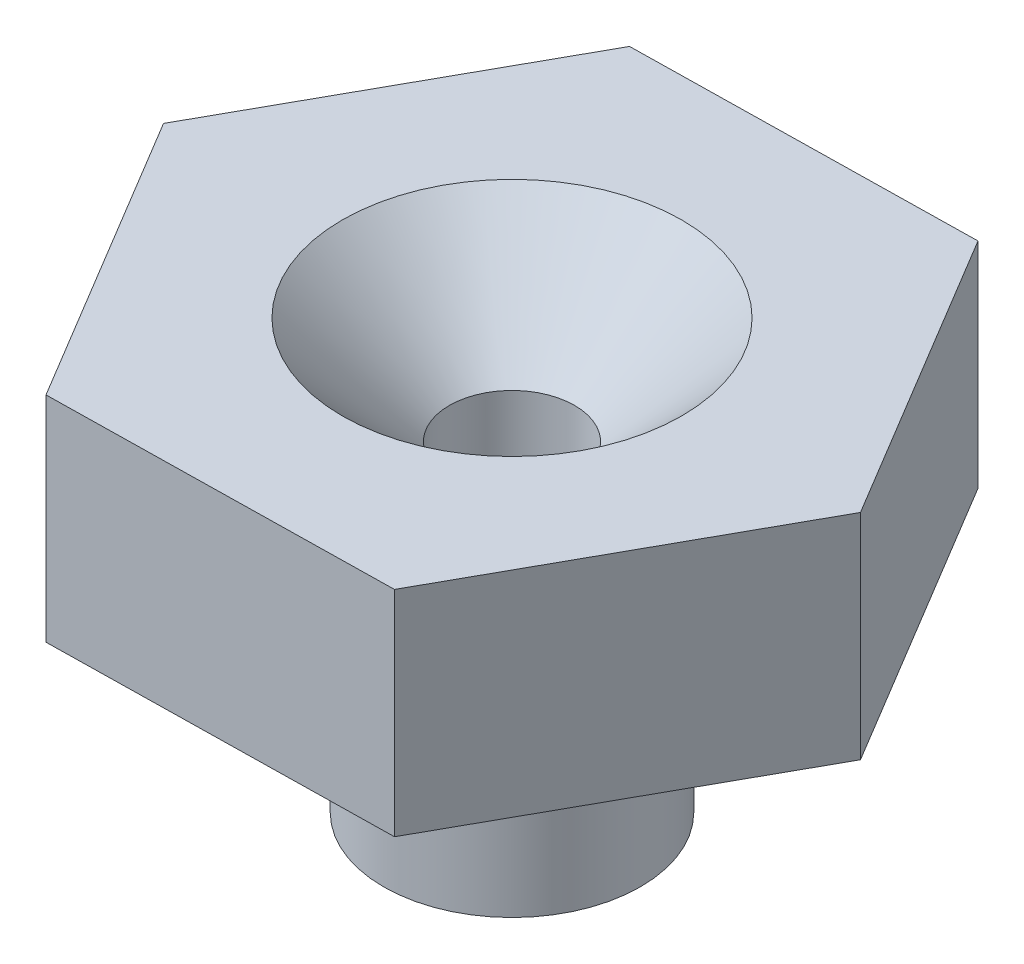
SolidWorks part; units mm, degrees
ref_plane "Front Plane" through (0, 0, 0) normal (0, 0, 1) x (1, 0, 0)
ref_plane "Top Plane" through (0, 0, 0) normal (0, 1, 0) x (1, 0, 0)
ref_plane "Right Plane" through (0, 0, 0) normal (1, 0, 0) x (0, 0, -1)
sketch "Sketch1" plane through (0, 0, 0) normal (0, 1, 0) x (1, 0, 0)
  line L1 (-15.9977, -0.2701) -> (-7.7649, -13.9895)
  line L2 (-7.7649, -13.9895) -> (8.2328, -13.7194)
  line L3 (8.2328, -13.7194) -> (15.9977, 0.2701)
  line L4 (15.9977, 0.2701) -> (7.7649, 13.9895)
  line L5 (7.7649, 13.9895) -> (-8.2328, 13.7194)
  line L6 (-8.2328, 13.7194) -> (-15.9977, -0.2701)
  circle A0 centre (0, 0) radius 16
  circle A1 centre (0, 0) radius 13.8564 construction
  point P3 (0, 0)
  point P11 (-8.2328, 13.7194)
  dimension "D1" = 32
extrude "Boss-Extrude1" add sketch "Sketch1" along normal blind 10 contours L5 L6 L1 L2 L3 L4 region at (0, 0, 0)
sketch "Sketch2" plane through (0, 0, 0) normal (0, -1, 0) x (1, 0, 0)
  circle A0 centre (0, 0) radius 6
  dimension "D1" = 12
extrude "Boss-Extrude2" add sketch "Sketch2" along normal blind 10
sketch "Sketch3" plane through (0, -10, 0) normal (0, -1, 0) x (1, 0, 0)
  circle A0 centre (0, 0) radius 2.925
  dimension "D1" = 5.85
extrude "Cut-Extrude1" cut sketch "Sketch3" against normal through all
fillet "Fillet1" radius 4 1 edges at (0, 0, -6)
chamfer "Chamfer1" distance 5 angle 45 1 edges at (0, 10, -2.925)
